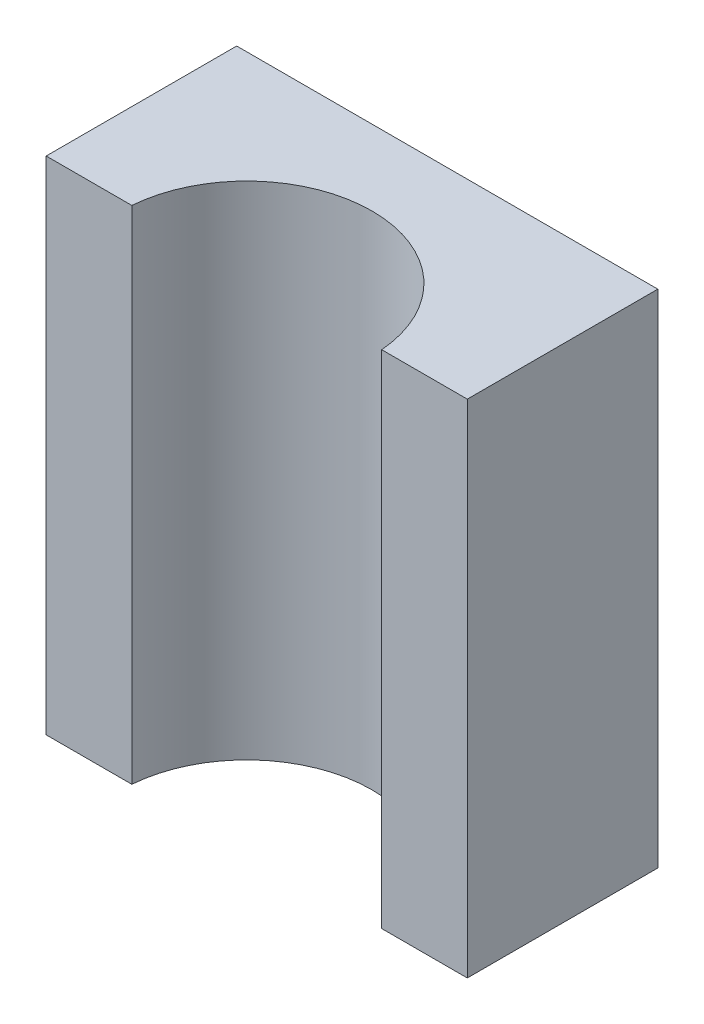
SolidWorks part; units mm, degrees
ref_plane "Płaszczyzna przednia" through (0, 0, 0) normal (0, 0, 1) x (1, 0, 0)
ref_plane "Płaszczyzna górna" through (0, 0, 0) normal (0, 1, 0) x (1, 0, 0)
ref_plane "Płaszczyzna prawa" through (0, 0, 0) normal (1, 0, 0) x (0, 0, -1)
sketch "Szkic1" plane through (0, 0, 0) normal (0, 1, 0) x (1, 0, 0)
  line L0 (0, -10.5) -> (0, 0) construction
  line L1 (21, -9.5) -> (12.4599, -9.5)
  line L2 (21, -9.5) -> (21, 9.5)
  line L3 (21, 9.5) -> (-21, 9.5)
  line L4 (-21, -9.5) -> (-21, 9.5)
  line L5 (21, -9.5) -> (-21, 9.5) construction
  line L6 (21, 9.5) -> (-21, -9.5) construction
  line L7 (-12.4599, -9.5) -> (-21, -9.5)
  arc A0 (12.4599, -9.5) -> (-12.4599, -9.5) centre (0, -10.5) ccw
  point P0 (0, 0)
  dimension "D3" = 12.5
  dimension "D1" = 42
  dimension "D2" = 20
  dimension "D4" = 1
extrude "Dodanie-wyciągnięcie1" add sketch "Szkic1" along normal mid plane 50
